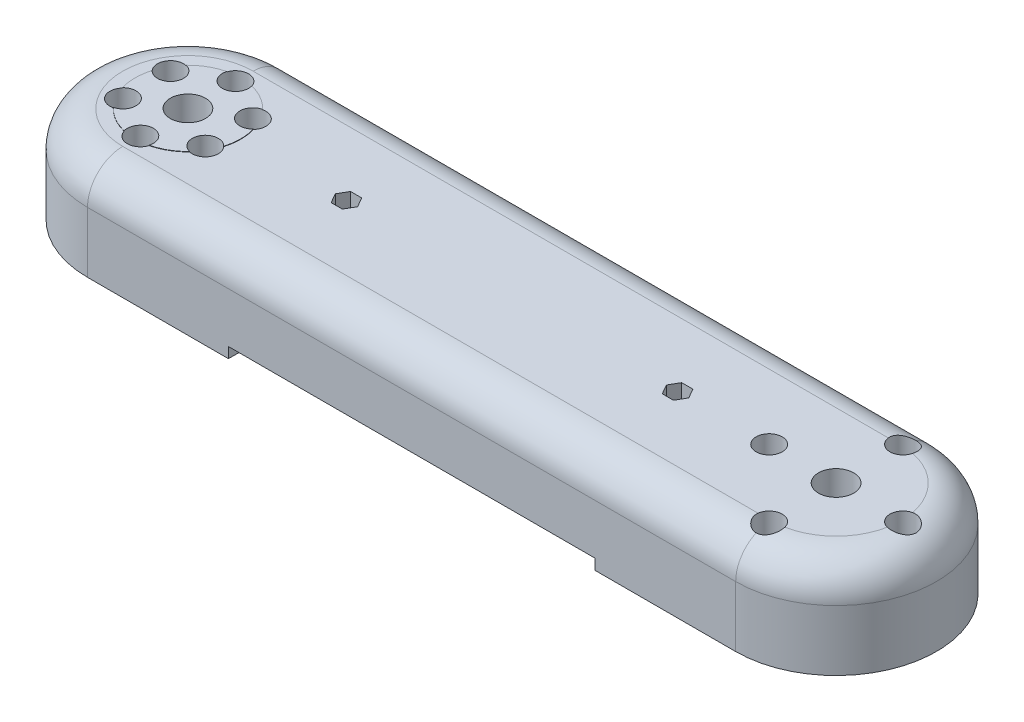
SolidWorks part; units mm, degrees
ref_plane "前视基准面" through (0, 0, 0) normal (0, 0, 1) x (1, 0, 0)
ref_plane "上视基准面" through (0, 0, 0) normal (0, 1, 0) x (1, 0, 0)
ref_plane "右视基准面" through (0, 0, 0) normal (1, 0, 0) x (0, 0, -1)
sketch "草图1" plane through (0, 0, 0) normal (0, 1, 0) x (1, 0, 0)
  line L1 (0, 28.5) -> (220, 28.5)
  line L3 (0, -28.5) -> (220, -28.5)
  line L4 (220, 28.5) -> (220, -28.5)
  arc A0 (0, 28.5) -> (0, -28.5) centre (0, 0) ccw
  dimension "D1" = 57
  dimension "D2" = 220
extrude "凸台-拉伸1" add sketch "草图1" along normal blind 27.2
sketch "草图2" plane through (0, 27.2, 0) normal (0, 1, 0) x (1, 0, 0)
  circle A0 centre (0, 0) radius 15
  dimension "D1" = 30
extrude "凸台-拉伸2" add sketch "草图2" along normal blind 0.1
sketch "草图3" plane through (0, 27.3, 0) normal (0, 1, 0) x (1, 0, 0)
  circle A0 centre (0, 0) radius 13.5 construction
  circle A1 centre (0, 13.5) radius 1.7
  circle A2 centre (11.6913, 6.75) radius 1.7
  circle A3 centre (11.6913, -6.75) radius 1.7
  circle A4 centre (0, -13.5) radius 1.7
  circle A5 centre (-11.6913, -6.75) radius 1.7
  circle A6 centre (-11.6913, 6.75) radius 1.7
  point P17 (0, 0)
  dimension "D1" = 27
  dimension "D2" = 3.4
extrude "切除-拉伸2" cut sketch "草图3" against normal blind 41
sketch "草图4" plane through (0, 27.3, 0) normal (0, 1, 0) x (1, 0, 0)
  circle A0 centre (0, 0) radius 5
  dimension "D1" = 10
extrude "切除-拉伸3" cut sketch "草图4" against normal blind 41
sketch "草图6" plane through (0, 27.2, 0) normal (0, 1, 0) x (1, 0, 0)
  line L0 (-40.0093, 0) -> (208.5283, 0) construction
  circle A0 centre (184, 0) radius 5
  circle A1 centre (0, 0) radius 5 construction
  circle A2 centre (184, 0) radius 19 construction
  circle A3 centre (184, 19) radius 1.7
  circle A4 centre (165, 0) radius 1.7
  circle A5 centre (184, -19) radius 1.7
  circle A6 centre (203, 0) radius 1.7
  point P19 (184, 0)
  dimension "D1" = 184
  dimension "D2" = 3.4
  dimension "D3" = 38
  dimension "D4" = 10
extrude "切除-拉伸4" cut sketch "草图6" against normal blind 60
sketch "草图8" plane through (0, 27.2, 0) normal (0, 1, 0) x (1, 0, 0)
  circle A0 centre (184, 19) radius 3.7
  circle A1 centre (203, 0) radius 3.7
  circle A2 centre (184, -19) radius 3.7
  circle A3 centre (165, 0) radius 3.7
  point P12 (184, 0)
  dimension "D1" = 7.4
extrude "切除-拉伸5" cut sketch "草图8" against normal offset from surface (11.2 mm away) 16 up to face at (203, 0, 1.7)
sketch "草图20" plane through (0, 27.2, 0) normal (0, 1, 0) x (1, 0, 0)
  line L1 (184, 28.5) -> (231.03, 28.5)
  line L2 (184, -28.5) -> (184, -33.5012)
  line L3 (184, -33.5012) -> (231.03, -33.5012)
  line L4 (231.03, 28.5) -> (231.03, -33.5012)
  arc A0 (184, -28.5) -> (184, 28.5) centre (184, 0) ccw
  dimension "D1" = 57
extrude "切除-拉伸6" cut sketch "草图20" against normal blind 40
sketch "草图24" plane through (0, 27.2, 0) normal (0, 1, 0) x (1, 0, 0)
  circle A0 centre (0, -13.5) radius 3.7
  circle A1 centre (-11.6913, -6.75) radius 3.7
  circle A2 centre (-11.6913, 6.75) radius 3.7
  circle A3 centre (0, 13.5) radius 3.7
  circle A4 centre (11.6913, 6.75) radius 3.7
  circle A5 centre (11.6913, -6.75) radius 3.7
  point P15 (0, 0)
  dimension "D1" = 7.4
extrude "切除-拉伸7" cut sketch "草图24" against normal offset from surface 14.5 and the other way blind 14.5 up to face at (203, 0, 1.7)
fillet "圆角1" radius 10 4 edges at (92, 27.2, -28.5) (212.5, 27.2, 0) (92, 27.2, 28.5) (-28.5, 27.2, 0)
sketch "草图25" plane through (0, 0, 0) normal (0, -1, 0) x (1, 0, 0)
  line L1 (40, -75.5559) -> (144, -75.5559)
  line L2 (40, -75.5559) -> (40, 72.9506)
  line L3 (40, 72.9506) -> (144, 72.9506)
  line L4 (144, -75.5559) -> (144, 72.9506)
  circle A0 centre (0, 0) radius 5 construction
  circle A1 centre (184, 0) radius 5 construction
  dimension "D1" = 40
  dimension "D2" = 40
extrude "切除-拉伸8" cut sketch "草图25" against normal blind 3
sketch "草图26" plane through (0, 3, 0) normal (0, -1, 0) x (1, 0, 0)
  line L1 (-37.8579, 0) -> (155.6929, 0) construction
  line L2 (40, 28.5) -> (40, -28.5) construction
  line L3 (50, -20) -> (134, -20)
  line L4 (50, -20) -> (50, 20)
  line L6 (50, 20) -> (134, 20)
  line L7 (134, -20) -> (134, 20)
  line L8 (50, -20) -> (134, 20) construction
  line L9 (50, 20) -> (134, -20) construction
  line L11 (144, -28.5) -> (144, 28.5) construction
  point P2 (92, 0)
  dimension "D1" = 10
  dimension "D2" = 10
  dimension "D3" = 40
extrude "切除-拉伸9" cut sketch "草图26" against normal blind 5
sketch "草图27" plane through (0, 3, 0) normal (0, -1, 0) x (1, 0, 0)
  line L0 (-36.9495, 0) -> (226.9466, 0) construction
  line L1 (40, 28.5) -> (40, -28.5) construction
  line L2 (134, -20) -> (134, 20) construction
  circle A0 centre (45, 0) radius 1.7
  circle A1 centre (139, 0) radius 1.7
  dimension "D1" = 3.4
  dimension "D2" = 3.4
  dimension "D3" = 5
  dimension "D4" = 5
extrude "切除-拉伸10" cut sketch "草图27" against normal blind 55
sketch "草图28" plane through (0, 27.2, 0) normal (0, 1, 0) x (1, 0, 0)
  line L1 (41.8246, 0) -> (43.4123, -2.75)
  line L2 (43.4123, -2.75) -> (46.5877, -2.75)
  line L3 (46.5877, -2.75) -> (48.1754, 0)
  line L4 (48.1754, 0) -> (46.5877, 2.75)
  line L5 (46.5877, 2.75) -> (43.4123, 2.75)
  line L6 (43.4123, 2.75) -> (41.8246, 0)
  line L7 (135.8246, 0) -> (137.4123, -2.75)
  line L8 (137.4123, -2.75) -> (140.5877, -2.75)
  line L9 (140.5877, -2.75) -> (142.1754, 0)
  line L10 (142.1754, 0) -> (140.5877, 2.75)
  line L11 (140.5877, 2.75) -> (137.4123, 2.75)
  line L12 (137.4123, 2.75) -> (135.8246, 0)
  circle A0 centre (45, 0) radius 2.75 construction
  circle A1 centre (139, 0) radius 2.75 construction
  dimension "D1" = 5.5
  dimension "D2" = 5.5
extrude "切除-拉伸11" cut sketch "草图28" against normal offset from surface (7.2 mm away) 20 up to face at (0, 0, -11.8)
